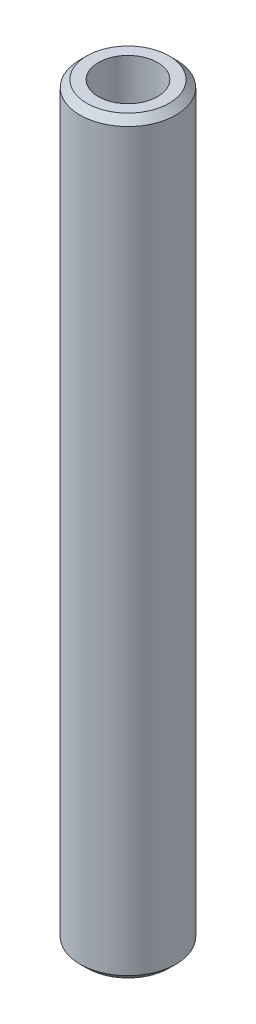
SolidWorks part; units mm, degrees
ref_plane "Front Plane" through (0, 0, 0) normal (0, 0, 1) x (1, 0, 0)
ref_plane "Top Plane" through (0, 0, 0) normal (0, 1, 0) x (1, 0, 0)
ref_plane "Right Plane" through (0, 0, 0) normal (1, 0, 0) x (0, 0, -1)
sketch "Sketch1" plane through (0, 0, 0) normal (0, 1, 0) x (1, 0, 0)
  circle A0 centre (0, 0) radius 37.5
  dimension "SHAFT_OD" = 75
extrude "Boss-Extrude1" add sketch "Sketch1" along normal blind 585.9595
sketch "Sketch2" plane through (0, 0, 0) normal (0, 1, 0) x (1, 0, 0)
  circle A0 centre (0, 0) radius 23.1603
  dimension "BORE_D" = 46.3207
extrude "Cut-Extrude1" cut sketch "Sketch2" along normal through all
chamfer "Chamfer1" distance 5.3354 angle 45 2 edges at (0, 585.9595, 37.5) (0, 0, 37.5)
